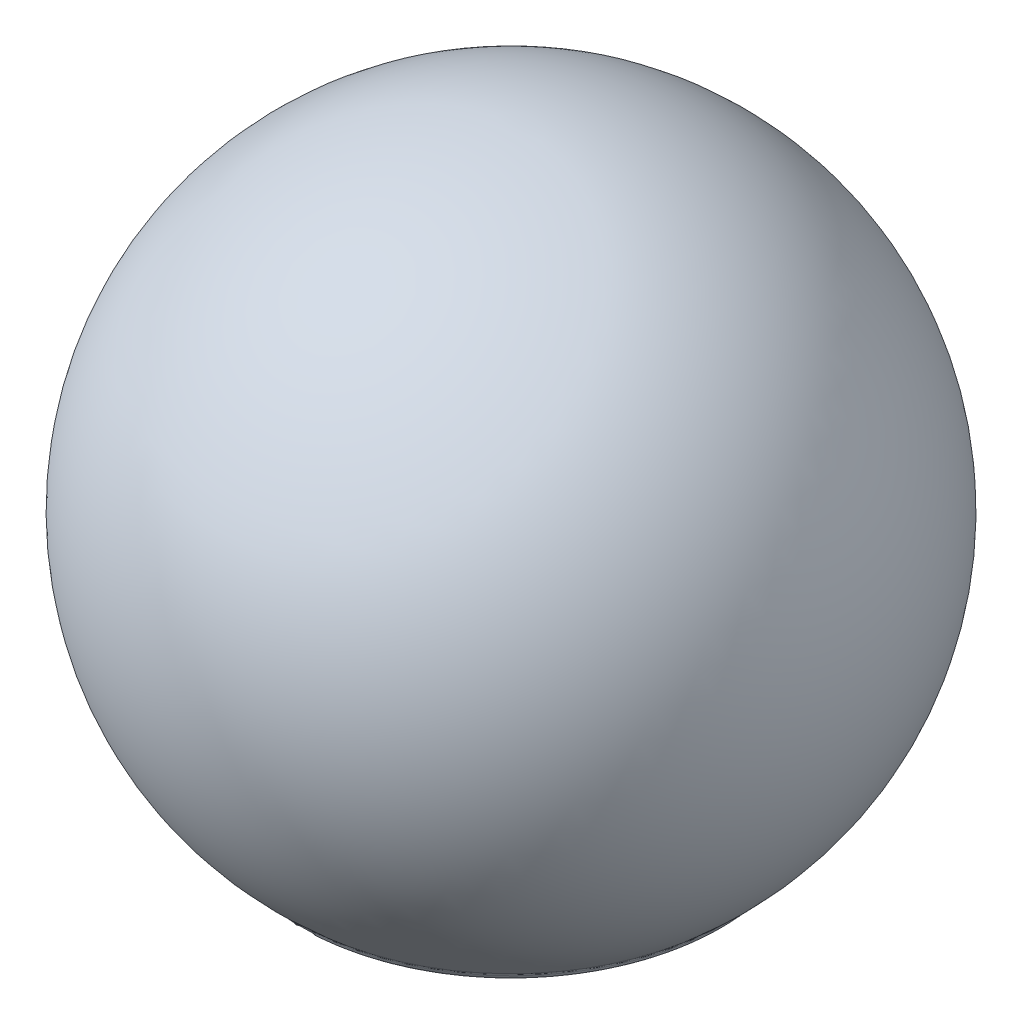
SolidWorks part; units mm, degrees
ref_plane "Front Plane" through (0, 0, 0) normal (0, 0, 1) x (1, 0, 0)
ref_plane "Top Plane" through (0, 0, 0) normal (0, 1, 0) x (1, 0, 0)
ref_plane "Right Plane" through (0, 0, 0) normal (1, 0, 0) x (0, 0, -1)
sketch "Sketch1" plane through (0, 0, 0) normal (0, 0, 1) x (1, 0, 0)
  line L0 (0, 74.75) -> (0, 73.175)
  line L1 (0, -73.175) -> (0, -74.75)
  arc A0 (0, -74.75) -> (0, 74.75) centre (0, 0) ccw
  arc A1 (0, -73.175) -> (0, 73.175) centre (0, 0) ccw
  dimension "D1" = 149.5
  dimension "D2" = 1.575
revolve "Revolve1" add sketch "Sketch1" angle 360 about L0
sketch "Sketch3" plane through (0, 0, 0) normal (0, 0, 1) x (1, 0, 0)
  line L0 (45.75, -57.1097) -> (-45.75, -57.1097)
  line L1 (0, -57.1097) -> (0, -74.75) construction
  line L5 (45.75, -57.1097) -> (48.2291, -57.1097)
  line L6 (48.2291, -57.1097) -> (48.2291, -74.75)
  line L8 (-48.2291, -74.75) -> (48.2291, -74.75)
  line L9 (-48.2291, -57.1097) -> (-48.2291, -74.75)
  line L10 (-45.75, -57.1097) -> (-48.2291, -57.1097)
  arc A1 (0, -73.175) -> (0, 73.175) centre (0, 0) ccw construction
  arc A2 (0, -74.75) -> (0, 74.75) centre (0, 0) ccw construction
  dimension "D1" = 45.75
extrude "Cut-Extrude1" cut sketch "Sketch3" against normal mid plane 130
sketch "Sketch4" plane through (0, 0, 0) normal (0, 0, 1) x (1, 0, 0)
  line L0 (48.2291, -57.1097) -> (48.2291, -58.6097)
  line L1 (48.2291, -58.6097) -> (45.75, -58.6097)
  line L2 (45.75, -58.6097) -> (45.75, -57.1097)
  line L3 (45.75, -57.1097) -> (48.2291, -57.1097)
  arc A0 (0, -74.75) -> (0, 74.75) centre (0, 0) ccw construction
  dimension "D1" = 1.5
revolve "Revolve2" add sketch "Sketch4" angle 360 about L1
fillet "Fillet1" radius 1.5 1 edges at (-48.2291, -58.6097, 0)
fillet "Fillet2" radius 1.5 1 edges at (-48.2291, -57.1097, 0)
fillet "Fillet3" radius 1.5 1 edges at (-45.75, -57.1097, 0)
